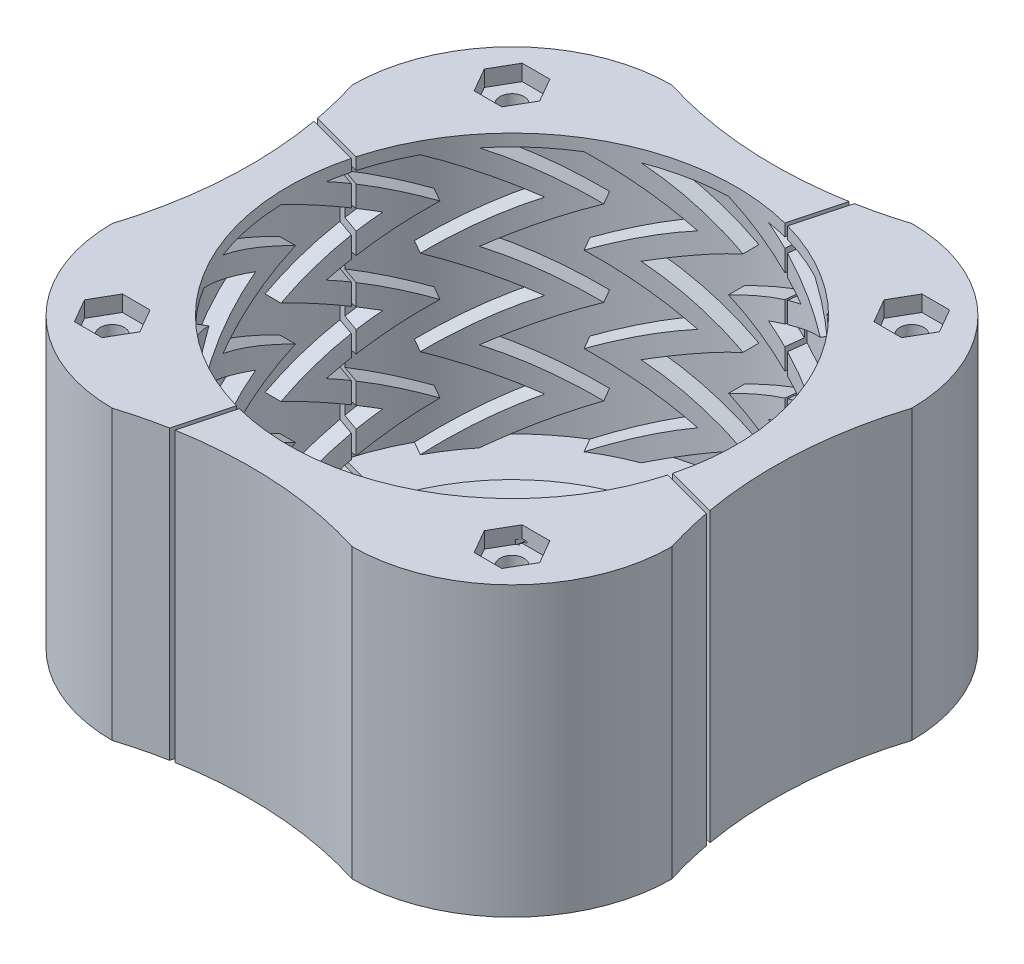
SolidWorks part; units mm, degrees
material "ABS"
ref_plane "Спереди" through (0, 0, 0) normal (0, 0, 1) x (1, 0, 0)
ref_plane "Сверху" through (0, 0, 0) normal (0, 1, 0) x (1, 0, 0)
ref_plane "Справа" through (0, 0, 0) normal (1, 0, 0) x (0, 0, -1)
sketch "Эскиз2" plane through (0, 0, 0) normal (0, 1, 0) x (1, 0, 0)
  line L1 (35, -35) -> (-35, -35)
  line L2 (35, -35) -> (35, 35)
  line L3 (35, 35) -> (-35, 35)
  line L4 (-35, -35) -> (-35, 35)
  line L5 (35, -35) -> (-35, 35) construction
  line L6 (35, 35) -> (-35, -35) construction
  point P0 (0, 0)
  dimension "D1" = 70
  dimension "D2" = 70
extrude "Бобышка-Вытянуть1" add sketch "Эскиз2" along normal blind 36
sketch "Эскиз3" plane through (0, 0, 0) normal (1, 0, 0) x (0, 0, -1)
  line L0 (0, 41.3522) -> (0, -3.1956) construction
  line L1 (-34.4708, 18) -> (34.6551, 18) construction
  line L3 (-28, 36) -> (-28, 2)
  line L4 (-23, 0) -> (0, 0)
  line L5 (0, 0) -> (0, 36)
  line L7 (-35, 36) -> (35, 36) construction
  line L8 (-35, 0) -> (35, 0) construction
  line L9 (-28, 36) -> (0, 36)
  line L10 (-28, 2) -> (-23, 2)
  line L11 (-23, 2) -> (-23, 0)
  line L12 (-23, 2) -> (-21, 0)
  line L13 (-40.4768, 0) -> (40.1693, 0) construction
  dimension "D2" = 56
  dimension "D3" = 2
  dimension "D4" = 42
  dimension "D5" = 2
revolve "Вырез-Повернуть1" cut sketch "Эскиз3" angle 360 about L5 region at (0, 18.2055, 13.8678)
fillet "Скругление1" radius 20 4 edges at (-35, 18, 35) (-35, 18, -35) (35, 18, -35) (35, 18, 35)
ref_plane "Плоскость5" through (23, 0, 0) normal (1, 0, 0) x (0, 0, -1)
sketch "Эскиз7" plane through (23, 0, 0) normal (1, 0, 0) x (0, 0, -1)
  line L0 (0, 44.0212) -> (0, -3.9515) construction
  line L1 (-41.4881, 2) -> (37.3044, 2) construction
  line L3 (-41.4881, 34.5) -> (37.3044, 34.5) construction
  line L4 (0.8993, 34.5) -> (10, 34.5)
  line L5 (0.8993, 34.5) -> (-10, 29.1667)
  line L6 (10, 34.5) -> (-0.8993, 29.1667)
  line L7 (-10, 29.1667) -> (-0.8993, 29.1667)
  line L8 (-10, 29.1667) -> (-0.8993, 29.1667)
  line L9 (-10, 29.1667) -> (0.8993, 23.8333)
  line L10 (-0.8993, 29.1667) -> (10, 23.8333)
  line L11 (0.8993, 23.8333) -> (10, 23.8333)
  line L12 (0.8993, 23.8333) -> (10, 23.8333)
  line L13 (0.8993, 23.8333) -> (-10, 18.5)
  line L14 (10, 23.8333) -> (-0.8993, 18.5)
  line L15 (-10, 18.5) -> (-0.8993, 18.5)
  line L16 (-0.8993, 18.5) -> (-10, 18.5)
  line L17 (-0.8993, 18.5) -> (10, 13.1667)
  line L18 (-10, 18.5) -> (0.8993, 13.1667)
  line L19 (10, 13.1667) -> (0.8993, 13.1667)
  line L20 (0.8993, 13.1667) -> (10, 13.1667)
  line L21 (0.8993, 13.1667) -> (-10, 7.8333)
  line L22 (10, 13.1667) -> (-0.8993, 7.8333)
  line L23 (-10, 7.8333) -> (-0.8993, 7.8333)
  line L24 (-0.8993, 7.8333) -> (-10, 7.8333)
  line L25 (-0.8993, 7.8333) -> (10, 2)
  line L26 (-10, 7.8333) -> (0.8993, 2)
  line L27 (10, 2) -> (0.8993, 2)
  line L28 (-10, 41.9456) -> (-10, -2.9296)
  line L29 (10, 41.9456) -> (10, -2.9296)
  line L30 (-35, 0) -> (-15, 0) construction
  dimension "D1" = 32.5
  dimension "D2" = 5.3333
  dimension "D3" = 5.3333
  dimension "D4" = 5.3333
  dimension "D5" = 5.3333
  dimension "D6" = 5.3333
  dimension "D7" = 4
  dimension "D8" = 20
  dimension "D9" = 2
extrude "Вырез-Вытянуть3" cut sketch "Эскиз7" along normal blind 8 contours L5 L7 L6 L4 | L9 L11 L10 L7 | L13 L15 L14 L11 | L19 L17 L15 L18 | L21 L23 L22 L19 | L27 L25 L23 L26 region at (23, 31.8333, 0) region at (23, 26.5, 0) region at (23, 21.1667, 0) region at (23, 15.8333, 0) region at (23, 10.5, 0) region at (23, 4.9167, 0)
pattern_circular "Круговой массив1" count 12 over 360 about axis through (0, 2, 0) along (0, -1, 0) of "Вырез-Вытянуть3"
sketch "Эскиз8" plane through (0, 0, 0) normal (1, 0, 0) x (0, 0, -1)
  line L0 (0, 47.5076) -> (0, -4.6512) construction
  line L2 (0, 34.5) -> (-30, 34.5)
  line L3 (0, 34.5) -> (0, 2)
  line L4 (0, 2) -> (-30, 2)
  line L5 (-30, 34.5) -> (-30, 2)
  line L6 (0.8993, 34.5) -> (10, 34.5) construction
  line L8 (-30, 34.5) -> (-32, 34.5)
  line L9 (-30, 34.5) -> (-30, 2)
  line L10 (-30, 2) -> (-32, 2)
  line L11 (-32, 34.5) -> (-32, 2)
  line L12 (-35, 0) -> (-15, 0) construction
  dimension "D1" = 60
  dimension "D2" = 2
  dimension "D3" = 2
revolve "Повернуть1" add sketch "Эскиз8" angle 360 about L0 region at (0, 18.25, 31)
sketch "Эскиз17" plane through (0, 0, 0) normal (0, 1, 0) x (1, 0, 0)
  line L1 (25, -25) -> (-25, -25)
  line L2 (25, -25) -> (25, 25)
  line L3 (25, 25) -> (-25, 25)
  line L4 (-25, -25) -> (-25, 25)
  line L5 (25, -25) -> (-25, 25) construction
  line L6 (25, 25) -> (-25, -25) construction
  circle A0 centre (-25, 25) radius 1.5
  circle A1 centre (25, 25) radius 1.5
  circle A2 centre (25, -25) radius 1.5
  circle A3 centre (-25, -25) radius 1.5
  point P0 (0, 0)
  dimension "D3" = 3
  dimension "D1" = 50
  dimension "D2" = 50
extrude "Вырез-Вытянуть12" cut sketch "Эскиз17" along normal through all contours A3 | A2 | A1 | A0
sketch "Эскиз18" plane through (0, 36, 0) normal (0, 1, 0) x (1, 0, 0)
  line L1 (-26.7321, 28) -> (-28.4641, 25)
  line L2 (-28.4641, 25) -> (-26.7321, 22)
  line L3 (-26.7321, 22) -> (-23.2679, 22)
  line L4 (-23.2679, 22) -> (-21.5359, 25)
  line L5 (-21.5359, 25) -> (-23.2679, 28)
  line L6 (-23.2679, 28) -> (-26.7321, 28)
  line L7 (23.2679, 28) -> (21.5359, 25)
  line L8 (21.5359, 25) -> (23.2679, 22)
  line L9 (23.2679, 22) -> (26.7321, 22)
  line L10 (26.7321, 22) -> (28.4641, 25)
  line L11 (28.4641, 25) -> (26.7321, 28)
  line L12 (26.7321, 28) -> (23.2679, 28)
  line L13 (23.2679, -22) -> (21.5359, -25)
  line L14 (21.5359, -25) -> (23.2679, -28)
  line L15 (23.2679, -28) -> (26.7321, -28)
  line L16 (26.7321, -28) -> (28.4641, -25)
  line L17 (28.4641, -25) -> (26.7321, -22)
  line L18 (26.7321, -22) -> (23.2679, -22)
  line L19 (-26.7321, -22) -> (-28.4641, -25)
  line L20 (-28.4641, -25) -> (-26.7321, -28)
  line L21 (-26.7321, -28) -> (-23.2679, -28)
  line L22 (-23.2679, -28) -> (-21.5359, -25)
  line L23 (-21.5359, -25) -> (-23.2679, -22)
  line L24 (-23.2679, -22) -> (-26.7321, -22)
  circle A0 centre (-25, 25) radius 3 construction
  circle A1 centre (25, 25) radius 3 construction
  circle A2 centre (25, -25) radius 3 construction
  circle A3 centre (-25, -25) radius 3 construction
  dimension "D1" = 6
extrude "Вырез-Вытянуть13" cut sketch "Эскиз18" against normal blind 2
sketch "Эскиз19" plane through (0, 0, 0) normal (0, 1, 0) x (1, 0, 0)
  line L1 (-26.7321, -28) -> (-23.2679, -28)
  line L2 (-23.2679, -28) -> (-21.5359, -25)
  line L3 (-21.5359, -25) -> (-23.2679, -22)
  line L4 (-23.2679, -22) -> (-26.7321, -22)
  line L5 (-26.7321, -22) -> (-28.4641, -25)
  line L6 (-28.4641, -25) -> (-26.7321, -28)
  line L7 (23.2679, -28) -> (26.7321, -28)
  line L8 (26.7321, -28) -> (28.4641, -25)
  line L9 (28.4641, -25) -> (26.7321, -22)
  line L10 (26.7321, -22) -> (23.2679, -22)
  line L11 (23.2679, -22) -> (21.5359, -25)
  line L12 (21.5359, -25) -> (23.2679, -28)
  line L13 (23.2679, 22) -> (26.7321, 22)
  line L14 (26.7321, 22) -> (28.4641, 25)
  line L15 (28.4641, 25) -> (26.7321, 28)
  line L16 (26.7321, 28) -> (23.2679, 28)
  line L17 (23.2679, 28) -> (21.5359, 25)
  line L18 (21.5359, 25) -> (23.2679, 22)
  line L19 (-26.7321, 22) -> (-23.2679, 22)
  line L20 (-23.2679, 22) -> (-21.5359, 25)
  line L21 (-21.5359, 25) -> (-23.2679, 28)
  line L22 (-23.2679, 28) -> (-26.7321, 28)
  line L23 (-26.7321, 28) -> (-28.4641, 25)
  line L24 (-28.4641, 25) -> (-26.7321, 22)
  circle A0 centre (-25, -25) radius 3 construction
  circle A1 centre (25, -25) radius 3 construction
  circle A2 centre (25, 25) radius 3 construction
  circle A3 centre (-25, 25) radius 3 construction
  dimension "D1" = 6
extrude "Вырез-Вытянуть15" cut sketch "Эскиз19" along normal blind 2
sketch "Эскиз20" plane through (0, 0, 0) normal (0, 1, 0) x (1, 0, 0)
  line L0 (10.0142, 37.3736) -> (-10.5294, -39.2964) construction
  line L1 (-37.3089, 10.2557) -> (37.4383, -9.7727)
  line L2 (0, 52.456) -> (0, -68.5486)
  line L3 (-9.7727, -37.4383) -> (-10.2557, -37.3089)
  line L4 (-9.7727, -37.4383) -> (10.2557, 37.3089)
  line L5 (10.2557, 37.3089) -> (9.7727, 37.4383)
  line L6 (-10.2557, -37.3089) -> (9.7727, 37.4383)
  line L7 (-9.7727, -37.4383) -> (9.7727, 37.4383) construction
  line L8 (10.2557, 37.3089) -> (-10.2557, -37.3089) construction
  line L9 (-37.4383, 9.7727) -> (37.3089, -10.2557)
  line L10 (-37.4383, 9.7727) -> (-37.3089, 10.2557)
  line L11 (37.3089, -10.2557) -> (37.4383, -9.7727)
  line L12 (10.2557, 37.3089) -> (-9.7727, -37.4383)
  line L13 (9.7727, 37.4383) -> (-10.2557, -37.3089)
  line L14 (9.7727, 37.4383) -> (10.2557, 37.3089)
  line L15 (-10.2557, -37.3089) -> (-9.7727, -37.4383)
  line L16 (37.3089, -10.2557) -> (-37.4383, 9.7727)
  line L17 (37.4383, -9.7727) -> (-37.3089, 10.2557)
  line L18 (37.4383, -9.7727) -> (37.3089, -10.2557)
  line L19 (-37.3089, 10.2557) -> (-37.4383, 9.7727)
  point P5 (0, 0)
  point P10 (0, 0)
  point P20 (10.0142, 37.3736)
  point P27 (0, 0)
  dimension "D1" = 0.5
  dimension "D2" = 4
  dimension "D3" = 15
extrude "Вырез-Вытянуть16" cut sketch "Эскиз20" along normal through all contours L4 L10 L6 L3 | L4 L5 L6 | L10 L6 | L9 L4 L10 region at (-18.8075, 0, -5.0395) region at (5.0561, 0, -18.8672) region at (-5.0561, 0, 18.8672) region at (18.8075, 0, 5.0395)
sketch "Эскиз21" plane through (0, 0, 0) normal (0, 1, 0) x (1, 0, 0)
  line L0 (-34.3367, 46.3515) -> (34.3367, 46.3515)
  line L1 (46.3515, 34.3367) -> (46.3515, -34.3367)
  line L2 (34.3367, -46.3515) -> (-34.3367, -46.3515)
  line L3 (-46.3515, -34.3367) -> (-46.3515, 34.3367)
  arc A0 (-15, 35) -> (-35, 15) centre (-15, 15) ccw construction
  arc A1 (35, 15) -> (15, 35) centre (15, 15) ccw construction
  arc A2 (15, -35) -> (35, -15) centre (15, -15) ccw construction
  arc A3 (-35, -15) -> (-15, -35) centre (-15, -15) ccw construction
  arc A4 (-15, 35) -> (-35, 15) centre (-15, 15) ccw
  arc A5 (35, 15) -> (15, 35) centre (15, 15) ccw
  arc A6 (15, -35) -> (35, -15) centre (15, -15) ccw
  arc A7 (-35, -15) -> (-15, -35) centre (-15, -15) ccw
  circle A8 centre (0, 82.697) radius 50
  circle A9 centre (82.697, 0) radius 50
  circle A10 centre (0, -82.697) radius 50
  circle A11 centre (-82.697, 0) radius 50
  point P31 (0, 0)
  dimension "D1" = 100
  dimension "D2" = 4
extrude "Вырез-Вытянуть17" cut sketch "Эскиз21" along normal through all contours A8 L0 | L3 A11 | L1 A9 | L2 A10 region at (0, 0, -40.8202) region at (-40.8202, 0, 0) region at (40.8202, 0, 0) region at (0, 0, 40.8202)
equation "\"D2@Эскиз2\"=\"D1@Эскиз2\""
equation "\"D4@Эскиз7\"= \"D2@Эскиз7\""
equation "\"D5@Эскиз7\"=\"D2@Эскиз7\""
equation "\"D6@Эскиз7\"=\"D2@Эскиз7\""
equation "\"D3@Эскиз7\"=\"D2@Эскиз7\""
equation "\"D2@Эскиз17\"=\"D1@Эскиз17\""
